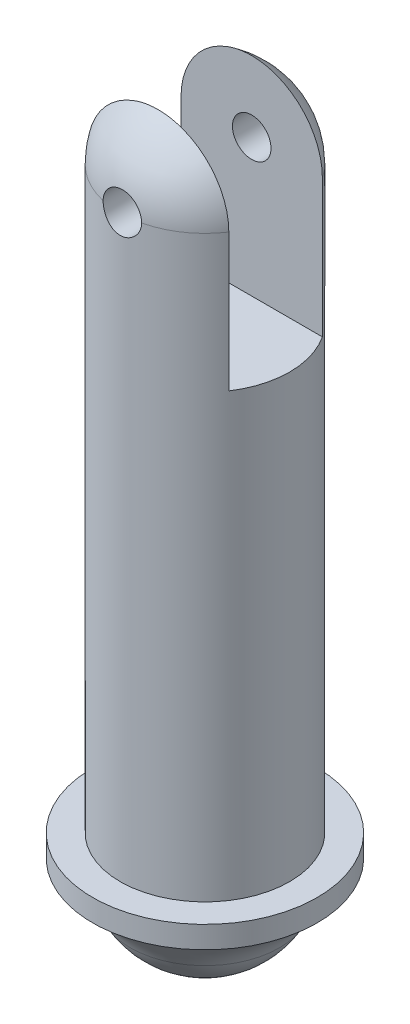
SolidWorks part; units mm, degrees
ref_plane "Front Plane" through (0, 0, 0) normal (0, 0, 1) x (1, 0, 0)
ref_plane "Top Plane" through (0, 0, 0) normal (0, 1, 0) x (1, 0, 0)
ref_plane "Right Plane" through (0, 0, 0) normal (1, 0, 0) x (0, 0, -1)
sketch "Sketch1" plane through (0, 0, 0) normal (0, 0, 1) x (1, 0, 0)
  line L0 (0, 0) -> (0, -13.8684) construction
  line L1 (1.9558, 0) -> (1.9558, -13.8684)
  line L2 (-1.9558, 0) -> (-1.9558, -13.8684)
  line L3 (-1.9558, -0.4445) -> (1.9558, -0.4445) construction
  line L4 (0, -0.4445) -> (0, -15.8242)
  line L5 (0, -0.4445) -> (0, 1.9558)
  arc A0 (1.9558, 0) -> (-1.9558, 0) centre (0, 0) ccw
  arc A1 (-1.9558, -13.8684) -> (1.9558, -13.8684) centre (0, -13.8684) ccw
  circle A2 centre (0, 0) radius 0.4445 construction
  point P3 (0, -6.9342)
  dimension "D1" = 1.9558
  dimension "D2" = 17.78
  dimension "D3" = 0.889
  dimension "D4" = 13.8684
revolve "Revolve1" add sketch "Sketch1" angle 360 about L0 region at (-0.9511, -6.9342, 0) reverse direction yes
sketch "Sketch2" plane through (0, 0, 0) normal (1, 0, 0) x (0, 0, -1)
  line L0 (0, -0.4445) -> (0, 1.9558) construction
  line L1 (0, -0.4445) -> (0, 1.9558)
  line L2 (0, 0) -> (0, -3.175)
  line L3 (1.0795, 2.1394) -> (-1.0795, 2.1394)
  line L4 (1.0795, 2.1394) -> (1.0795, -3.175)
  line L5 (1.0795, -3.175) -> (-1.0795, -3.175)
  line L6 (-1.0795, 2.1394) -> (-1.0795, -3.175)
  line L7 (1.0795, 2.1394) -> (-1.0795, -3.175) construction
  line L8 (1.0795, -3.175) -> (-1.0795, 2.1394) construction
  line L9 (0, -0.4445) -> (0, -15.8242) construction
  point P2 (0, -0.5178)
  dimension "D1" = 2.159
  dimension "D3" = 3.175
extrude "Cut-Extrude1" cut sketch "Sketch2" against normal through all and the other way through all contours L3 L6 L5 L4
sketch "Sketch3" plane through (0, 0, 0) normal (0, 0, 1) x (1, 0, 0)
  circle A0 centre (0, 0) radius 0.4445 construction
  circle A1 centre (0, 0) radius 0.4445
extrude "Cut-Extrude2" cut sketch "Sketch3" against normal through all and the other way through all
ref_plane "Plane2" through (0, -13.8684, 0) normal (0, -1, 0) x (-1, 0, 0)
sketch "Sketch4" plane through (0, -13.8684, 0) normal (0, -1, 0) x (-1, 0, 0)
  circle A0 centre (0, 0) radius 1.9558 construction
  circle A1 centre (0, 0) radius 1.9558
  circle A2 centre (0, 0) radius 2.5908
  dimension "D1" = 0.635
extrude "Boss-Extrude8" add sketch "Sketch4" against normal blind 0.508
fillet "Fillet1" radius 2.54 1 edges at (0, -13.8684, -1.9558)
